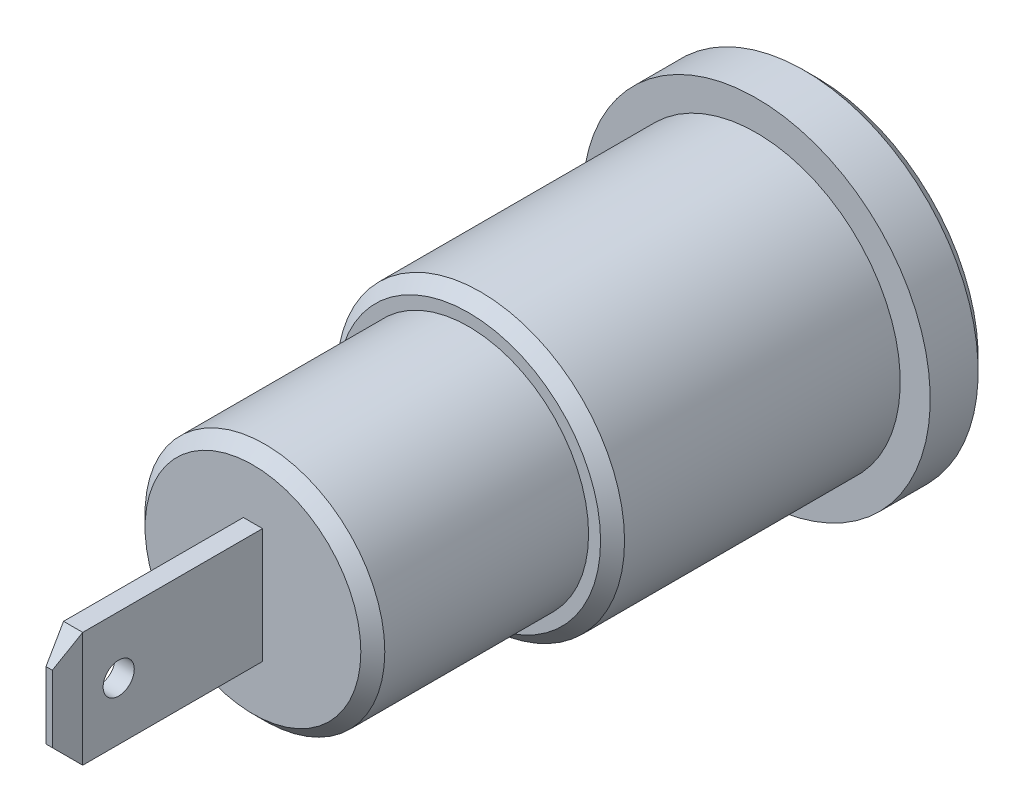
SolidWorks part; units mm, degrees
ref_plane "Plan de face" through (0, 0, 0) normal (0, 0, 1) x (1, 0, 0)
ref_plane "Plan de dessus" through (0, 0, 0) normal (0, 1, 0) x (1, 0, 0)
ref_plane "Plan de droite" through (0, 0, 0) normal (1, 0, 0) x (0, 0, -1)
sketch "Esquisse1" plane through (0, 0, 0) normal (0, 0, 1) x (1, 0, 0)
  circle A0 centre (0, 0) radius 6
  dimension "D1" = 12
extrude "Boss.-Extru.1" add sketch "Esquisse1" along normal blind 12
sketch "Esquisse2" plane through (0, 0, 12) normal (0, 0, 1) x (1, 0, 0)
  circle A0 centre (0, 0) radius 5
  dimension "D1" = 10
extrude "Boss.-Extru.2" add sketch "Esquisse2" along normal blind 9
sketch "Esquisse3" plane through (0, 0, 0) normal (0, 0, -1) x (-1, 0, 0)
  circle A0 centre (0, 0) radius 7.25
  dimension "D1" = 14.5
extrude "Boss.-Extru.3" add sketch "Esquisse3" along normal blind 2.5
sketch "Esquisse4" plane through (0, 0, -2.5) normal (0, 0, -1) x (-1, 0, 0)
  circle A0 centre (0, 0) radius 2
  dimension "D1" = 4
extrude "Enlèv. mat.-Extru.1" cut sketch "Esquisse4" against normal blind 20
sketch "Esquisse9" plane through (0, 0, -2.5) normal (0, 0, -1) x (-1, 0, 0)
  circle A0 centre (0, 0) radius 2.1
  circle A2 centre (0, 0) radius 2 construction
  dimension "D1" = 0.1
extrude "Enlèv. mat.-Extru.4" cut sketch "Esquisse9" against normal blind 5.5
sketch "Esquisse6" plane through (0, 0, -2.5) normal (0, 0, -1) x (-1, 0, 0)
  circle A0 centre (0, 0) radius 2.5
  circle A1 centre (0, 0) radius 4.25
  dimension "D1" = 5
  dimension "D2" = 8.5
extrude "Enlèv. mat.-Extru.2" cut sketch "Esquisse6" against normal blind 10
chamfer "Chanfrein1" distance 0.5 angle 45 4 edges at (-7.25, 0, -2.5) (6, 0, 12) (-4.25, 0, -2.5) (5, 0, 21)
chamfer "Chanfrein2" distance 0.2 angle 45 1 edges at (-2.5, 0, -2.5)
sketch "Esquisse8" plane through (0, 0, 0) normal (1, 0, 0) x (0, 0, -1)
  line L1 (-21, -2.4) -> (-28.5, -2.4)
  line L2 (-21, -2.4) -> (-21, 2.4)
  line L3 (-21, 2.4) -> (-28.5, 2.4)
  line L4 (-29.5, -1.4) -> (-29.5, 1.4)
  line L5 (-12, 0) -> (-21, 0) construction
  line L7 (-12, 5) -> (-12, -5) construction
  line L8 (-21, 5) -> (-21, -5) construction
  line L9 (2.5, -6.75) -> (2.5, 6.75) construction
  line L10 (-28.5, 2.4) -> (-29.5, 1.4)
  line L11 (-28.5, -2.4) -> (-29.5, -1.4)
  line L12 (-21, 0) -> (-27, 0) construction
  circle A0 centre (-27, 0) radius 0.65
  point P1 (-29.5, 2.4)
  point P3 (-29.5, -2.4)
  point P11 (-21, 0)
  dimension "D3" = 1.3
  dimension "D1" = 4.8
  dimension "D2" = 32
  dimension "D4" = 6
extrude "Boss.-Extru.4" add sketch "Esquisse8" along normal blind 0.4 and the other way blind 0.4
chamfer "Chanfrein3" distance 1 angle 15 1 edges at (0.4, 0, 29.5) first distance on face at (0.4, 0, 26.3333)
chamfer "Chanfrein4" distance 1 angle 15 1 edges at (-0.4, 0, 29.5) first distance on face at (-0.4, 0, 26.35)
